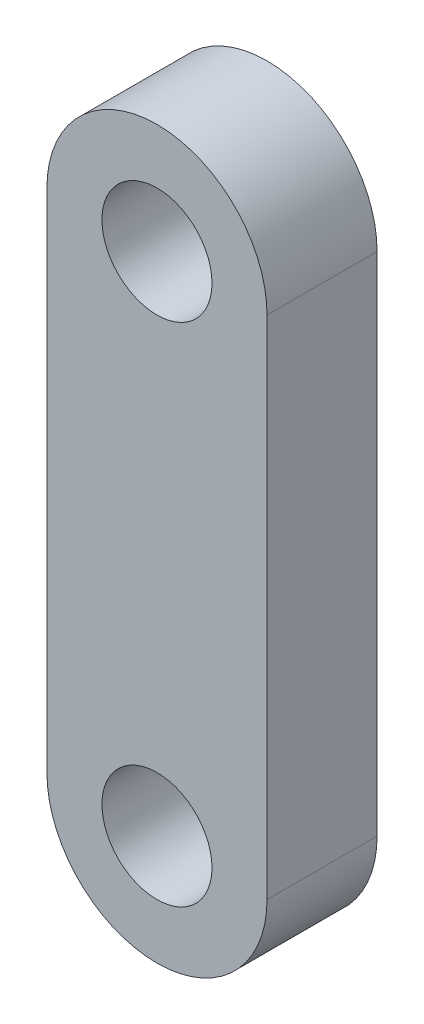
SolidWorks part; units mm, degrees
ref_plane "前基準面" through (0, 0, 0) normal (0, 0, 1) x (1, 0, 0)
ref_plane "上基準面" through (0, 0, 0) normal (0, 1, 0) x (1, 0, 0)
ref_plane "右基準面" through (0, 0, 0) normal (1, 0, 0) x (0, 0, -1)
sketch "草圖1" plane through (0, 0, 0) normal (0, 0, 1) x (1, 0, 0)
  line L0 (0, 0) -> (0, 23) construction
  line L1 (5, 0) -> (5, 23)
  line L2 (-5, 0) -> (-5, 23)
  arc A0 (5, 0) -> (-5, 0) centre (0, 0) cw
  arc A1 (5, 23) -> (-5, 23) centre (0, 23) ccw
  circle A2 centre (0, 0) radius 2.5
  circle A3 centre (0, 23) radius 2.5
  dimension "D4" = 5
  dimension "D1" = 23
  dimension "D2" = 5
  dimension "D3" = 5
extrude "填料-伸長1" add sketch "草圖1" along normal mid plane 5
sketch "草圖2" [suppressed] plane through (0, 0, 0) normal (0, 0, 1) x (1, 0, 0)
  line L0 (5, 71.8226) -> (5, -10.3016) construction
  line L1 (-13.5017, 71.8226) -> (-13.5017, -8.0919) construction
  line L2 (-5.027, 59.4253) -> (-13.5017, 59.4253)
  line L3 (-5.027, -0.4253) -> (-13.5017, -0.4253)
  arc A0 (-5, 0) -> (5, 0) centre (0, 0) ccw construction
  circle A1 centre (0, 0) radius 2.5 construction
  arc A2 (5, 59) -> (-5, 59) centre (0, 59) ccw construction
  circle A3 centre (0, 59) radius 2.5 construction
  arc A4 (-0.8399, 4.9289) -> (0.8399, -4.9289) centre (0, 0) ccw construction
  circle A5 centre (0, 0) radius 2.5 construction
  arc A6 (0.8399, 63.9289) -> (-0.8399, 54.0711) centre (0, 59) ccw construction
  circle A7 centre (0, 59) radius 2.5 construction
  arc A8 (-0.8399, 54.0711) -> (-0.8399, 4.9289) centre (-5.027, 29.5) cw construction
  arc A9 (0.8399, 63.9289) -> (0.8399, -4.9289) centre (-5.027, 29.5) cw construction
  arc A10 (-5.027, 59.4253) -> (-5.027, -0.4253) centre (-5.027, 29.5) cw
  arc A11 (0, 59) -> (0, 0) centre (-5.027, 29.5) cw construction
  point P2 (19.8982, 29.5)
  dimension "D1" = 10
  dimension "D3" = 5
  dimension "D2" = 5
ref_plane "平面1" [suppressed] through (-13.5017, 59.4253, 0) normal (-1, 0, 0) x (0, 0, 1)
sketch "草圖4" [suppressed] plane through (-13.5017, 59.4253, 0) normal (-1, 0, 0) x (0, 0, 1)
  line L0 (7.5, 5) -> (-7.5, -5) construction
  line L1 (-7.5, 5) -> (7.5, 5)
  line L2 (-7.5, 5) -> (-7.5, -5)
  line L3 (-7.5, -5) -> (7.5, -5)
  line L4 (7.5, 5) -> (7.5, -5)
  point P4 (0, 0)
  dimension "D1" = 15
  dimension "D2" = 10
sketch "草圖5" [suppressed] plane through (-13.5017, 59.4253, 0) normal (-1, 0, 0) x (0, 0, 1)
  line L0 (2.5, -54.8505) -> (-2.5, -64.8505) construction
  line L1 (-2.5, -54.8505) -> (2.5, -54.8505)
  line L2 (-2.5, -54.8505) -> (-2.5, -64.8505)
  line L3 (-2.5, -64.8505) -> (2.5, -64.8505)
  line L4 (2.5, -54.8505) -> (2.5, -64.8505)
  point P4 (0, -59.8505)
  dimension "D1" = 5
  dimension "D2" = 10
sketch "草圖13" [suppressed] plane through (0, 0, 0) normal (0, 0, 1) x (1, 0, 0)
  line L3 (-13.5017, 64.4253) -> (-5.027, 64.4253)
  line L4 (-13.5017, 71.8226) -> (-13.5017, -8.0919) construction
  line L5 (-13.5017, -5.4253) -> (-5.027, -5.4253)
  line L6 (-5.027, 59.4253) -> (-5.027, 64.4253) construction
  arc A0 (-5.027, 64.4253) -> (-5.027, -5.4253) centre (-5.027, 29.5) cw
sketch "草圖14" [suppressed] plane through (0, 0, 0) normal (1, 0, 0) x (0, 0, -1)
  line L0 (-7.5, 64.4253) -> (-4.028, 48.6369)
  line L1 (-2.5, -5.4253) -> (-2.5, 34.5747)
  line L2 (0, -5.4253) -> (0, 42.6172) construction
  line L3 (2.5, -5.4253) -> (-2.5, -5.4253) construction
  line L4 (0, 71.8226) -> (0, -8.0919) construction
  line L5 (2.5, -5.4253) -> (2.5, 34.5747) construction
  line L6 (7.5, 64.4253) -> (4.028, 48.6369) construction
  arc A0 (-4.028, 48.6369) -> (-2.5, 34.5747) centre (-67.9726, 34.5747) cw
  arc A1 (4.028, 48.6369) -> (2.5, 34.5747) centre (67.9726, 34.5747) ccw construction
  dimension "D1" = 40
curve "曲線1" [suppressed]
sketch "草圖15" [suppressed] plane through (0, 0, 0) normal (0, 0, 1) x (1, 0, 0)
  line L0 (-13.5017, 54.4253) -> (-5.027, 54.4253)
  line L1 (-13.5017, 71.8226) -> (-13.5017, -8.0919) construction
  line L2 (-13.5017, 4.5747) -> (-5.027, 4.5747)
  arc A0 (-5.027, 4.5747) -> (-5.027, 54.4253) centre (-5.027, 29.5) ccw
sketch "草圖16" [suppressed] plane through (0, 0, 0) normal (1, 0, 0) x (0, 0, -1)
  line L0 (-2.5, 4.5747) -> (-2.5, 34.5747)
  line L1 (-2.5, -5.4253) -> (-2.5, 34.5747) construction
  line L2 (-7.5, 54.4253) -> (-4.5451, 46.2499)
  line L3 (2.5, -5.4253) -> (-2.5, -5.4253) construction
  line L4 (0, -5.4253) -> (0, 45.5813) construction
  line L5 (0, 71.8226) -> (0, -8.0919) construction
  line L6 (7.5, 54.4253) -> (4.5451, 46.2499) construction
  line L7 (2.5, 4.5747) -> (2.5, 34.5747) construction
  arc A0 (-4.5451, 46.2499) -> (-2.5, 34.5747) centre (-36.8475, 34.5747) cw
  arc A1 (4.5451, 46.2499) -> (2.5, 34.5747) centre (36.8475, 34.5747) ccw construction
  dimension "D1" = 40
curve "曲線2" [suppressed]
sketch "草圖18" [suppressed] plane through (0, 0, 0) normal (1, 0, 0) x (0, 0, -1)
  line L0 (2.5, -5.4253) -> (2.5, 34.5747) construction
  line L1 (7.5, 64.4253) -> (4.028, 48.6369) construction
  line L2 (2.5, -5.4253) -> (2.5, 34.5747)
  line L3 (7.5, 64.4253) -> (4.028, 48.6369)
  arc A0 (4.028, 48.6369) -> (2.5, 34.5747) centre (67.9726, 34.5747) ccw construction
  arc A1 (4.028, 48.6369) -> (2.5, 34.5747) centre (67.9726, 34.5747) ccw
curve "曲線3"
sketch "草圖13<3>" plane through (0, 0, 0) normal (0, 0, 1) x (1, 0, 0) same geometry as "草圖13"
sketch "草圖19" [suppressed] plane through (0, 0, 0) normal (1, 0, 0) x (0, 0, -1)
  line L0 (2.5, 4.5747) -> (2.5, 34.5747) construction
  line L1 (7.5, 54.4253) -> (4.5451, 46.2499) construction
  line L2 (2.5, 4.5747) -> (2.5, 34.5747)
  line L3 (7.5, 54.4253) -> (4.5451, 46.2499)
  arc A0 (4.5451, 46.2499) -> (2.5, 34.5747) centre (36.8475, 34.5747) ccw construction
  arc A1 (4.5451, 46.2499) -> (2.5, 34.5747) centre (36.8475, 34.5747) ccw
curve "曲線4"
sketch "草圖15<3>" plane through (0, 0, 0) normal (0, 0, 1) x (1, 0, 0) same geometry as "草圖15"
loft "疊層拉伸3" [suppressed] add profiles "草圖4", "草圖5"
sketch "草圖20" [suppressed] plane through (0, 0, 0) normal (0, 0, 1) x (1, 0, 0)
  line L0 (0.8399, 63.9289) -> (0.8399, 71.7019)
  line L1 (0.8399, 71.7019) -> (-28.6138, 67.8154)
  line L2 (-28.6138, 67.8154) -> (-22.2616, 48.2861)
  line L3 (-22.2616, 48.2861) -> (-0.8399, 54.0711)
  line L4 (-0.8399, 4.9289) -> (-24.2544, 10.2977)
  line L5 (-24.2544, 10.2977) -> (-19.7706, -14.2391)
  line L6 (-19.7706, -14.2391) -> (0.8399, -4.9289)
  circle A6 centre (0, 0) radius 2.5 construction
  circle A7 centre (0, 59) radius 2.5 construction
  circle A8 centre (0, 0) radius 2.5
  circle A9 centre (0, 59) radius 2.5
  arc A10 (-0.8399, 4.9289) -> (0.8399, -4.9289) centre (0, 0) ccw construction
  arc A11 (0.8399, 63.9289) -> (-0.8399, 54.0711) centre (0, 59) ccw construction
  arc A12 (-0.8399, 4.9289) -> (0.8399, -4.9289) centre (0, 0) ccw
  arc A13 (0.8399, 63.9289) -> (-0.8399, 54.0711) centre (0, 59) ccw
extrude "除料-伸長5" [suppressed] cut sketch "草圖20" against normal mid plane 50
sketch "草圖23" [suppressed] plane through (0, 0, 0) normal (0, 1, 0) x (1, 0, 0)
  line L0 (-5, -2.5) -> (-5, 2.5)
  line L1 (-5, 7.4972) -> (-5, -7.4972) construction
  line L2 (-5, 2.5) -> (7, 2.5)
  line L3 (9.5, 0) -> (0, 0) construction
  line L4 (-5, -2.5) -> (7, -2.5)
  arc A0 (7, 2.5) -> (9.5, 0) centre (7, 0) cw
  arc A1 (7, -2.5) -> (9.5, 0) centre (7, 0) ccw
  point P12 (-5, 0)
  dimension "D1" = 5
  dimension "D2" = 12
extrude "除料-伸長7" [suppressed] cut sketch "草圖23" along normal blind 50 from offset 45
